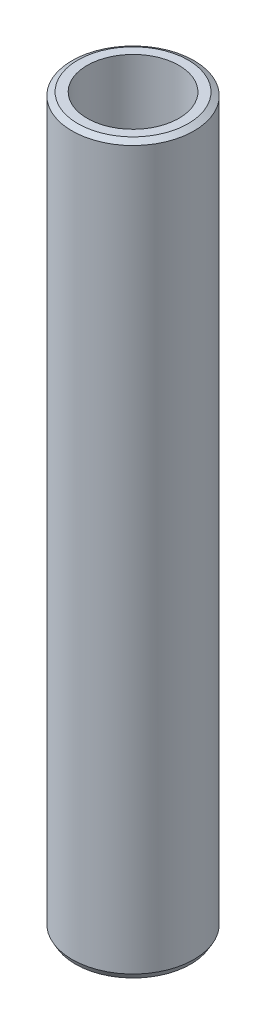
SolidWorks part; units mm, degrees
ref_plane "Front Plane" through (0, 0, 0) normal (0, 0, 1) x (1, 0, 0)
ref_plane "Top Plane" through (0, 0, 0) normal (0, 1, 0) x (1, 0, 0)
ref_plane "Right Plane" through (0, 0, 0) normal (1, 0, 0) x (0, 0, -1)
sketch "Sketch1" plane through (0, 0, 0) normal (0, 1, 0) x (1, 0, 0)
  circle A0 centre (0, 0) radius 37.5
  dimension "SHAFT_OD" = 75
extrude "Boss-Extrude1" add sketch "Sketch1" along normal blind 446.829
sketch "Sketch2" plane through (0, 0, 0) normal (0, 1, 0) x (1, 0, 0)
  circle A0 centre (0, 0) radius 28.2193
  dimension "BORE_D" = 56.4385
extrude "Cut-Extrude1" cut sketch "Sketch2" along normal through all
chamfer "Chamfer1" distance 2.0726 angle 60 2 edges at (0, 446.829, 37.5) (0, 0, 37.5) first distance on face at (0, 446.829, 37.5) first distance on face at (0, 0, 28.2193)
